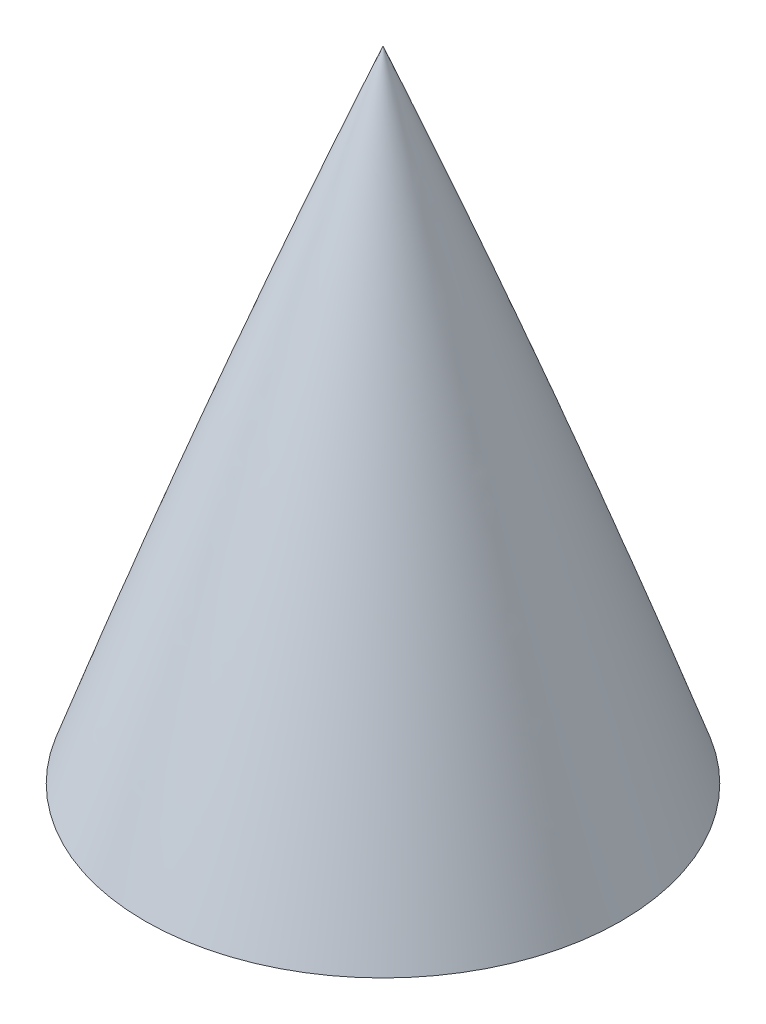
SolidWorks part; units mm, degrees
material "PVB"
ref_plane "Front Plane" through (0, 0, 0) normal (0, 0, 1) x (1, 0, 0)
ref_plane "Top Plane" through (0, 0, 0) normal (0, 1, 0) x (1, 0, 0)
ref_plane "Right Plane" through (0, 0, 0) normal (1, 0, 0) x (0, 0, -1)
sketch "Sketch2" plane through (0, 0, 0) normal (0, 0, 1) x (1, 0, 0)
  line L0 (0, 0) -> (0, 381) construction
  line L1 (-78.359, 0) -> (-70.485, 0)
  line L2 (0, 381) -> (0, 375.92)
  line L3 (0, 375.92) -> (0, 0)
  line L4 (0, 0) -> (-70.485, 0)
  arc A0 (0, 381) -> (-78.359, 0) centre (1014.6868, -26.2452) ccw
  dimension "D1" = 381
  dimension "D2" = 5.08
  dimension "D3" = 78.359
  dimension "D4" = 7.874
revolve "Revolve1" add sketch "Sketch2" angle 360 about L2
sketch "Sketch3" plane through (0, 0, 0) normal (0, -1, 0) x (1, 0, 0)
  circle A0 centre (0, 0) radius 88.9
  circle A1 centre (0, 0) radius 86.995
  dimension "D1" = 177.8
extrude "Boss-Extrude1" [suppressed] add sketch "Sketch3" along normal blind 35.56
sketch "Sketch7" plane through (0, 0, 0) normal (0, -1, 0) x (1, 0, 0)
  circle A0 centre (-188.315, 83.0177) radius 421.4958
extrude "Cut-Extrude2" cut sketch "Sketch7" against normal blind 330.2
sketch "Sketch8" plane through (0, 330.2, 0) normal (0, -1, 0) x (-1, 0, 0)
  circle A0 centre (0, 0) radius 2.413
  dimension "D1" = 4.826
extrude "Cut-Extrude3" cut sketch "Sketch8" against normal blind 12.7
